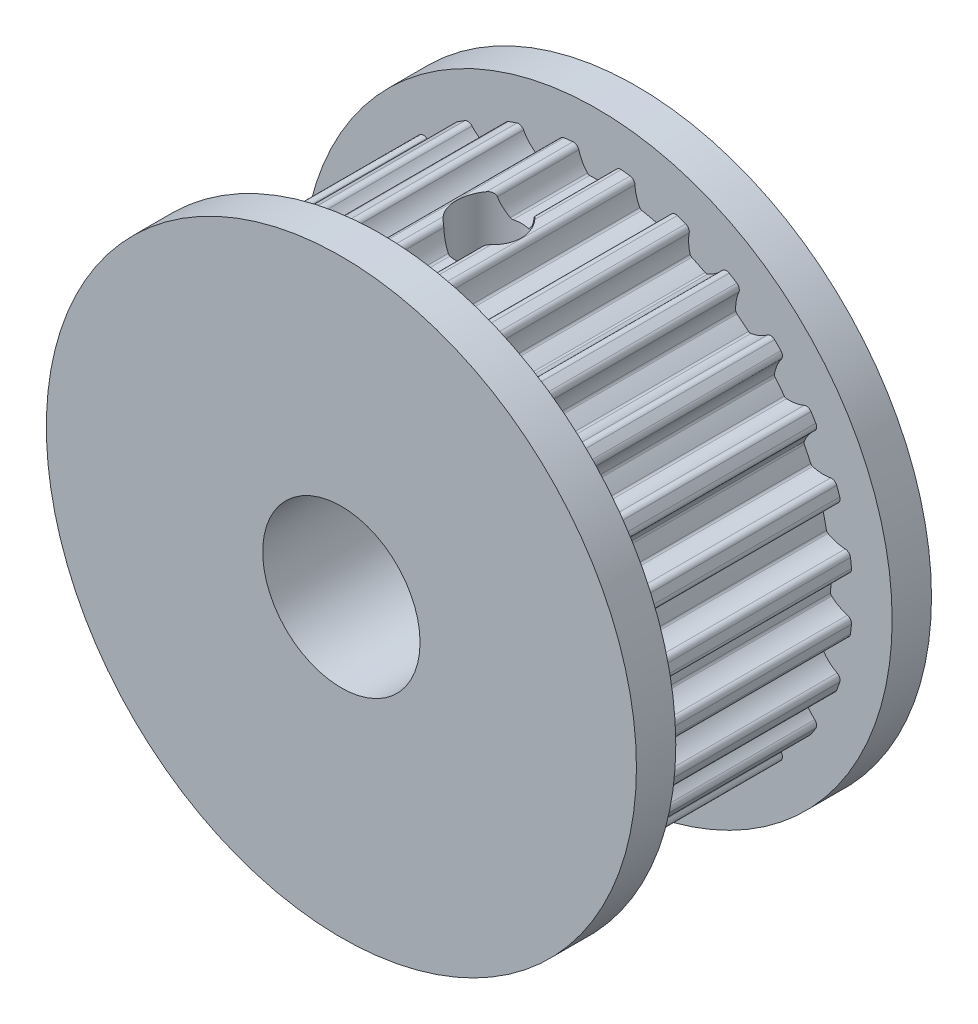
SolidWorks part; units mm, degrees
material "6061-T6 (SS)"
ref_plane "前基準面" through (0, 0, 0) normal (0, 0, 1) x (1, 0, 0)
ref_plane "上基準面" through (0, 0, 0) normal (0, 1, 0) x (1, 0, 0)
ref_plane "右基準面" through (0, 0, 0) normal (1, 0, 0) x (0, 0, -1)
sketch "草圖1" plane through (0, 0, 0) normal (0, 0, 1) x (1, 0, 0)
  circle A0 centre (0, 0) radius 12.99
  dimension "D1" = 25.98
extrude "填料-伸長1" add sketch "草圖1" along normal mid plane 11
sketch "草圖2" plane through (0, 0, 5.5) normal (0, 0, 1) x (1, 0, 0)
  line L0 (0, 0) -> (0, 13.244) construction
  line L1 (-0.975, 13.244) -> (0.975, 13.244) construction
  arc A0 (-0.3775, 11.874) -> (0.3775, 11.874) centre (0, 0) cw
  circle A1 centre (0, 0) radius 12.99 construction
  arc A2 (-1.2277, 12.9319) -> (-0.931, 12.7265) centre (-1.2012, 12.6531) cw
  arc A3 (-0.931, 12.7265) -> (-0.4938, 11.9236) centre (0.975, 13.244) ccw
  arc A4 (-0.4938, 11.9236) -> (-0.3775, 11.874) centre (-0.3822, 12.0239) ccw
  arc A5 (0.4938, 11.9236) -> (0.3775, 11.874) centre (0.3822, 12.0239) cw
  arc A6 (0.931, 12.7265) -> (0.4938, 11.9236) centre (-0.975, 13.244) cw
  arc A7 (1.2277, 12.9319) -> (0.931, 12.7265) centre (1.2012, 12.6531) ccw
  point P6 (0, 11.88)
  point P18 (0, 12.99)
  dimension "D1" = 1.11
  dimension "D2" = 0.15
  dimension "D3" = 1.975
  dimension "D4" = 0.28
  dimension "D5" = 1.95
  dimension "D6" = 0.254
extrude "除料-伸長1" cut sketch "草圖2" against normal through all and the other way through all flip side to cut
pattern_circular "環狀複製排列1" count 28 over 360 about axis through (0, 0, 5.5) along (0, 0, 1) of "除料-伸長1"
sketch "草圖3" plane through (0, 0, 5.5) normal (0, 0, 1) x (1, 0, 0)
  circle A0 centre (0, 0) radius 15
  dimension "D1" = 30
extrude "填料-伸長2" add sketch "草圖3" along normal blind 2
mirror "鏡射1" about plane through (0, 0, 0) normal (0, 0, 1) of "填料-伸長2"
sketch "草圖4" plane through (0, 0, 7.5) normal (0, 0, 1) x (1, 0, 0)
  circle A0 centre (0, 0) radius 4
  dimension "D1" = 8
extrude "除料-伸長2" cut sketch "草圖4" against normal through all
hole_wizard "M4x0.7 螺紋孔1" positions "草圖5" profile "草圖6" tap size "M4x0.7" standard "Ansi Metric" end condition through all
sketch "草圖5" plane through (0, 0, 0) normal (0, 1, 0) x (1, 0, 0)
  point P0 (0, 0)
sketch "草圖6" plane through (0, 0, 0) normal (1, 0, 0) x (0, 0, -1)
  line L0 (0, 0) -> (0, 15)
  line L1 (0, 15) -> (1.65, 15)
  line L2 (1.65, 15) -> (1.65, 0)
  line L5 (1.65, 0) -> (0, 0)
  line L11 (0, -6.35) -> (0, 107.95) construction
  dimension "貫穿螺孔鑽直徑" = 3.3
  dimension "貫穿螺孔鑽深度" = 15
pattern_circular "環狀複製排列2" count 2 every 90 about axis through (0, 0, 7.5) along (0, 0, 1) of "M4x0.7 螺紋孔1"
